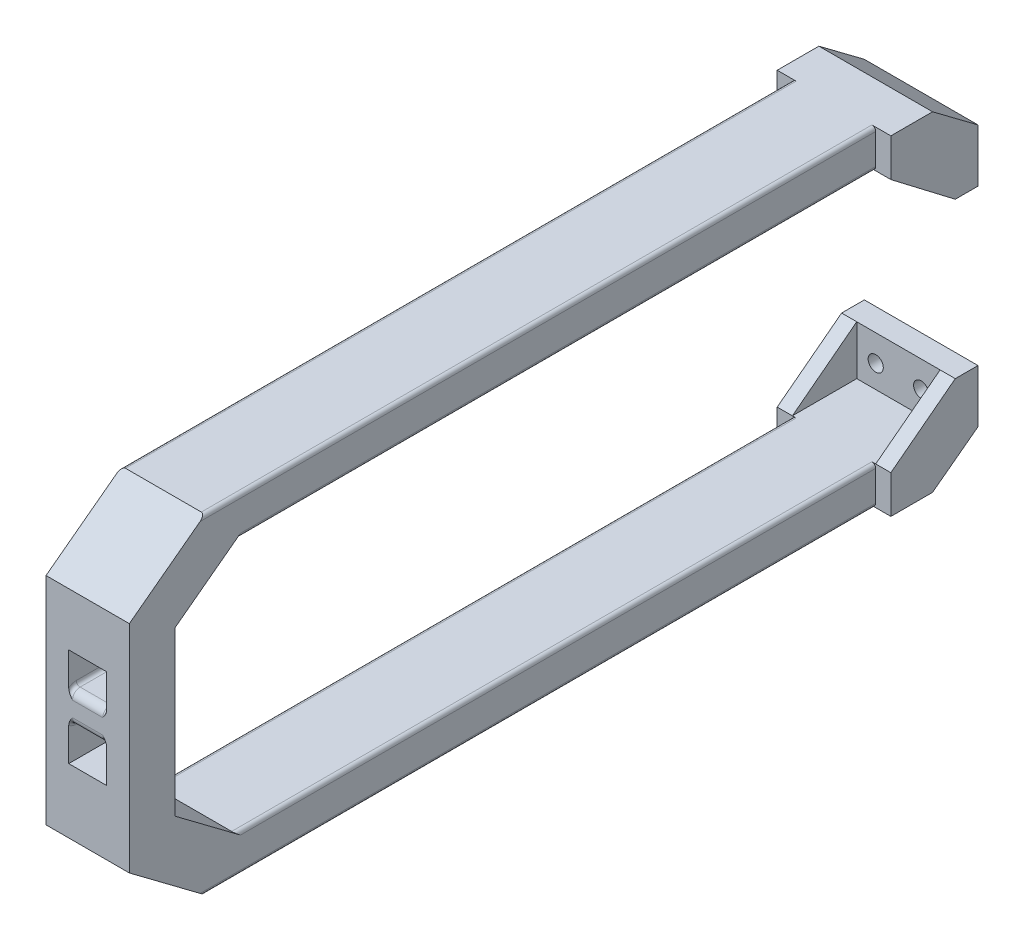
SolidWorks part; units mm, degrees
ref_plane "Front Plane" through (0, 0, 0) normal (0, 0, 1) x (1, 0, 0)
ref_plane "Top Plane" through (0, 0, 0) normal (0, 1, 0) x (1, 0, 0)
ref_plane "Right Plane" through (0, 0, 0) normal (1, 0, 0) x (0, 0, -1)
sketch "Sketch1" plane through (0, 0, 0) normal (0, 0, 1) x (1, 0, 0)
  line L1 (0, 0) -> (30, 0)
  line L2 (0, 0) -> (0, 87)
  line L3 (0, 87) -> (30, 87)
  line L4 (30, 0) -> (30, 87)
  point P5 (0, 0)
  point P6 (0, 0)
  point P7 (0, 0)
  point P8 (0, 0)
  point P9 (0, 0)
  point P10 (0, 0)
  point P11 (0, 0)
  point P12 (0, 0)
extrude "Boss-Extrude1" add sketch "Sketch1" along normal blind 220
sketch "Sketch2" plane through (30, 0, 0) normal (1, 0, 0) x (0, 0, -1)
  line L3 (-192, 77) -> (-23, 77)
  line L5 (0, 87) -> (-12, 87)
  line L7 (-12, 87) -> (0, 78)
  line L8 (0, 0) -> (0, 87) construction
  line L9 (0, 87) -> (0, 78)
  line L10 (-208, 65) -> (-208, 22)
  line L12 (-192, 10) -> (-23, 10)
  line L13 (-23, 77) -> (-6, 64)
  line L15 (-6, 23) -> (-23, 10)
  line L18 (0, 0) -> (-12, 0)
  line L19 (-220, 0) -> (0, 0) construction
  line L20 (-12, 0) -> (0, 9)
  line L21 (0, 9) -> (0, 0)
  line L22 (0, 64) -> (-6, 64)
  line L23 (-6, 23) -> (0, 23)
  line L24 (0, 23) -> (0, 64)
  line L25 (-208, 65) -> (-192, 77)
  line L26 (-220, 87) -> (-220, 72)
  line L27 (-220, 0) -> (-220, 87) construction
  line L28 (-220, 87) -> (0, 87) construction
  line L29 (-220, 72) -> (-200, 87)
  line L30 (-200, 87) -> (-220, 87)
  line L31 (-220, 0) -> (-220, 15)
  line L32 (-220, 15) -> (-200, 0)
  line L33 (-200, 0) -> (-220, 0)
  line L34 (-208, 22) -> (-192, 10)
  point P15 (0, 0)
  point P30 (0, 0)
  point P31 (0, 0)
  point P32 (0, 0)
  point P33 (0, 0)
  point P34 (0, 0)
  point P35 (0, 0)
  point P37 (0, 0)
  point P38 (0, 0)
  point P39 (0, 0)
  point P40 (0, 0)
  point P41 (0, 0)
  point P42 (0, 0)
  point P44 (0, 0)
  point P45 (0, 0)
  point P46 (0, 0)
  point P47 (0, 0)
  point P48 (0, 0)
  point P49 (0, 0)
  point P50 (0, 0)
  point P51 (0, 0)
  point P52 (0, 0)
  point P53 (0, 0)
  point P54 (0, 0)
  point P55 (0, 0)
  point P56 (0, 0)
  point P57 (0, 0)
  point P60 (0, 0)
  point P61 (0, 0)
  point P62 (0, 0)
extrude "Cut-Extrude1" cut sketch "Sketch2" against normal through all
sketch "Sketch3" plane through (0, 64, 0) normal (0, -1, 0) x (-1, 0, 0)
  line L1 (-4, -6) -> (-26, -6)
  line L2 (-4, -6) -> (-4, -28)
  line L3 (-4, -28) -> (-26, -28)
  line L4 (-26, -6) -> (-26, -28)
  point P4 (0, 0)
  point P5 (-20.0963, 0)
  point P6 (0, 0)
  point P7 (0, 0)
  point P8 (0, 0)
  point P9 (0, 0)
  point P10 (0, 0)
  point P11 (0, 0)
  point P12 (0, 0)
  point P13 (0, 0)
  point P14 (0, 0)
  point P15 (-4.0477, 0)
  point P16 (0, 0)
  point P17 (0, 0)
  point P18 (0, 0)
  point P19 (0, 0)
  point P20 (0, 0)
  point P21 (0, 0)
  point P22 (0, 0)
extrude "Cut-Extrude2" cut sketch "Sketch3" against normal blind 13
sketch "Sketch4" plane through (0, 23, 0) normal (0, 1, 0) x (1, 0, 0)
  line L0 (0, -6) -> (30, -6) construction
  line L1 (4, -6) -> (26, -6)
  line L2 (4, -6) -> (4, -28)
  line L3 (4, -28) -> (26, -28)
  line L4 (26, -6) -> (26, -28)
  point P6 (0, 0)
  point P7 (0, 0)
  point P8 (0, 0)
  point P9 (0, 0)
  point P10 (0, 0)
  point P11 (0, 0)
extrude "Cut-Extrude3" cut sketch "Sketch4" against normal blind 13
sketch "Sketch5" plane through (0, 0, 220) normal (0, 0, 1) x (1, 0, 0)
  line L1 (10, 58) -> (20, 58)
  line L2 (10, 58) -> (10, 49)
  line L3 (10, 49) -> (20, 49)
  line L4 (20, 58) -> (20, 49)
  line L5 (10, 32) -> (20, 32)
  line L6 (10, 32) -> (10, 41)
  line L7 (10, 41) -> (20, 41)
  line L8 (20, 32) -> (20, 41)
  point P8 (0, 0)
  point P9 (0, 0)
  point P10 (0, 0)
  point P11 (0, 0)
  point P12 (0, 0)
  point P13 (0, 0)
  point P14 (0, 0)
  point P15 (0, 0)
  point P16 (0, 0)
  point P17 (0, 0)
  point P18 (0, 0)
  point P19 (0, 0)
  point P20 (0, 0)
  point P21 (0, 0)
  point P22 (0, 0)
  point P23 (0, 0)
  point P24 (0, 0)
  point P25 (0, 0)
  point P26 (0, 0)
  point P27 (0, 0)
  point P28 (0, 0)
  point P29 (0, 0)
  point P30 (0, 0)
  point P31 (0, 0)
  point P32 (0, 0)
extrude "Cut-Extrude4" cut sketch "Sketch5" against normal up to next
sketch "Sketch6" plane through (0, 0, 220) normal (0, 0, 1) x (1, 0, 0)
  line L0 (0, 0) -> (30, 0) construction
  line L1 (0, 87) -> (4, 87)
  line L2 (0, 87) -> (0, 0)
  line L3 (0, 0) -> (4, 0)
  line L4 (4, 87) -> (4, 0)
  line L6 (30, 87) -> (26, 87)
  line L7 (30, 87) -> (30, 0)
  line L8 (30, 0) -> (26, 0)
  line L9 (26, 87) -> (26, 0)
  point P12 (0, 0)
  point P14 (0, 0)
extrude "Cut-Extrude5" cut sketch "Sketch6" against normal blind 197
hole_wizard "Ø4.0mm Dowel Hole1" positions "Sketch7" profile "Sketch8" hole size "Ø4.0" standard "JIS" end condition through all
sketch "Sketch7" plane through (0, 0, 6) normal (0, 0, 1) x (1, 0, 0)
  point P0 (9, 16)
  point P2 (9, 71)
  point P8 (21, 71)
  point P10 (21, 16)
sketch "Sketch8" plane through (9, 16, 6) normal (1, 0, 0) x (0, -1, 0)
  line L0 (0, 0) -> (0, 6)
  line L1 (0, 6) -> (2, 6)
  line L2 (2, 6) -> (2, 0)
  line L5 (2, 0) -> (0, 0)
  line L11 (0, -6.35) -> (0, 107.95) construction
  dimension "Thru Hole Dia." = 4
  dimension "Thru Hole Depth" = 6
fillet "Fillet1" radius 2 4 edges at (15, 49, 208) (15, 41, 208) (15, 49, 220) (15, 41, 220)
fillet "Fillet2" radius 1 20 edges at (20, 49, 214) (10, 49, 214) (10, 41, 214) (20, 41, 214) (10, 48.4142, 208.5858) (20, 48.4142, 208.5858) (20, 41.5858, 208.5858) (10, 41.5858, 208.5858) (20, 48.4142, 219.4142) (10, 48.4142, 219.4142) (10, 41.5858, 219.4142) (20, 41.5858, 219.4142) (4, 10, 107.5) (26, 10, 107.5) (4, 0, 111.5) (26, 0, 111.5) (4, 87, 111.5) (26, 87, 111.5) (26, 77, 107.5) (4, 77, 107.5)
